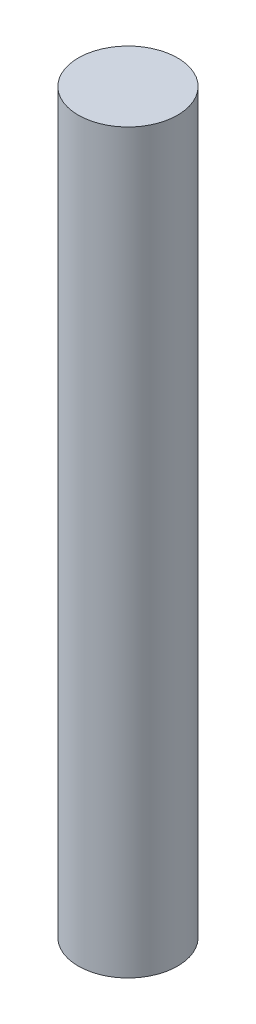
SolidWorks part; units mm, degrees
ref_plane "Front Plane" through (0, 0, 0) normal (0, 0, 1) x (1, 0, 0)
ref_plane "Top Plane" through (0, 0, 0) normal (0, 1, 0) x (1, 0, 0)
ref_plane "Right Plane" through (0, 0, 0) normal (1, 0, 0) x (0, 0, -1)
sketch "Sketch1" plane through (0, 0, 0) normal (0, 1, 0) x (1, 0, 0)
  circle A0 centre (0, 0) radius 27
  dimension "D1" = 54
extrude "Boss-Extrude1" add sketch "Sketch1" along normal blind 401
equation "\"Motor_Length\"= 401mm"
equation "\"Motor_OD\"= 54mm"
equation "\"D1@Sketch1\"=\"Motor_OD\""
equation "\"D1@Boss-Extrude1\"=\"Motor_Length\""
equation "\"Aft_Section_Length\"= 30in"
equation "\"Mid_Coupler_Length\"= 12in"
equation "\"AB_Coupler_OD_Length\"= 1in"
equation "\"AB_Coupling_Section_Length\"= 0.375in"
equation "\"AB_Coupler_Length\"= \"AB_Coupler_OD_Length\" + \"AB_Coupling_Section_Length\" * 2"
equation "\"Cutout_Angle\"= 60"
equation "\"AB_Paddle_Height\"= 0.375in"
equation "\"AB_Coupler_Num_Screws\"= 4"
equation "\"Num_Cutouts\"= 4"
equation "\"AB_Coupler_OD\"= 4.024in"
equation "\"AB_Coupler_ID\"= 3.7in"
equation "\"AB_Coupler_Surface_Diameter\"= 3.899in"
equation "\"AB_Coupling_Screw_Diameter\"= 0.1065in"
equation "\"AB_Central_Bushing_Length\"= 0.75in"
equation "\"Lead_Screw_Dist\"= 2in"
equation "\"Lead_Screw_Diam\"= 0.375in"
equation "\"Lead_Screw_Length\"= \"Mid_Coupler_Length\" + 2*0.375in + 2*0.5in"
equation "\"Paddle_Pin_Offset\"= 0.25in"
equation "\"Paddle_Pin_Radius\"= 2.25*2/3in"
equation "\"Paddle_Gear_OD\"= 3.2in"
equation "\"Fwd_BKHD_From_Top\"= 18in"
equation "\"Body_Tube_OD\"= 4.024in"
equation "\"Body_Tube_ID\"= 3.90in"
equation "\"Coupler_OD\"= 3.899in"
equation "\"Coupler_ID\"= 3.755in"
equation "\"Fwd_Section_Length\"= 25in"
equation "\"Mid_Section_Length\"= 6in"
equation "\"Aft_Upper_Tube_Length\"= 10in"
equation "\"Aft_Lower_Tube_Length\"= 18in"
equation "\"Nosecone_Coupler_Length\"= 5in"
equation "\"Avionics_Bulkhead_Thickness\"= 0.25in"
equation "\"Avionics_Bulkhead_Lip\"= 0.125in"
equation "\"Avionics_Board_Length\"= \"Mid_Coupler_Length\" - 2*\"Avionics_Bulkhead_Lip\""
equation "\"Lead_Screw_Hole_Diam\"= (27/64)*1in"
equation "\"Centering_Ring_Cutout_Dia\"=1.5in"
